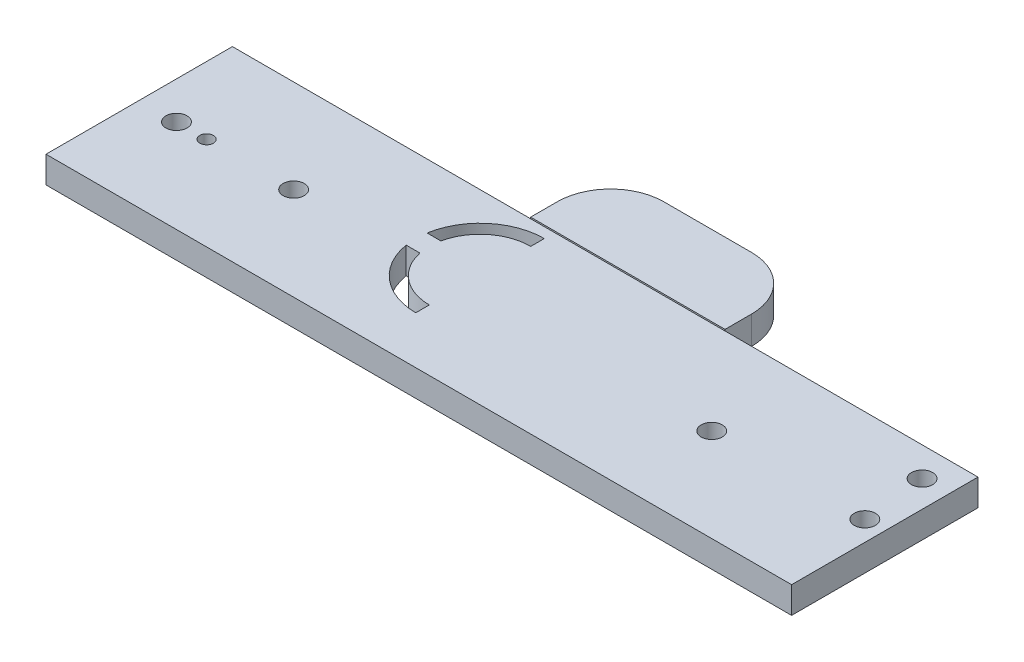
SolidWorks part; units mm, degrees
ref_plane "Front Plane" through (0, 0, 0) normal (0, 0, 1) x (1, 0, 0)
ref_plane "Top Plane" through (0, 0, 0) normal (0, 1, 0) x (1, 0, 0)
ref_plane "Right Plane" through (0, 0, 0) normal (1, 0, 0) x (0, 0, -1)
sketch "Sketch1" plane through (0, 0, 0) normal (0, 1, 0) x (1, 0, 0)
  line L1 (0, 0) -> (280, 0)
  line L2 (0, 0) -> (0, 70)
  line L3 (0, 70) -> (280, 70)
  line L4 (280, 0) -> (280, 70)
  circle A0 centre (14, 35) radius 3.9688
  circle A1 centre (58, 35) radius 3.9688
  circle A2 centre (215, 35) radius 3.9687
  circle A3 centre (272.5, 35) radius 3.9687
  circle A5 centre (270, 59) radius 3.9688
  circle A6 centre (58, 35) radius 27.5336
  circle A7 centre (215, 35) radius 27.5336
  circle A8 centre (25.3189, 35) radius 2.55
  circle A9 centre (215, 35) radius 50.34
  dimension "D3" = 7.9375
  dimension "D6" = 58
  dimension "D7" = 7.9375
  dimension "D9" = 7.9375
  dimension "D12" = 7.5
  dimension "D13" = 7.9375
  dimension "D15" = 7.9375
  dimension "D18" = 55.0672
  dimension "D19" = 55.0672
  dimension "D20" = 5.1
  dimension "D23" = 100.68
  dimension "D1" = 280
  dimension "D2" = 70
  dimension "D4" = 35
  dimension "D5" = 14
  dimension "D8" = 35
  dimension "D10" = 215
  dimension "D11" = 35
  dimension "D14" = 35
  dimension "D16" = 11
  dimension "D17" = 10
  dimension "D21" = 35
  dimension "D22" = 32.6811
extrude "Boss-Extrude7" add sketch "Sketch1" along normal blind 10 contours A9 L3 L2 L1 A8 A6 A0 | A9 L1 L4 L3 A3 A5 | A7 A2 | L1 A9 L3 A7 | A6 A1 region at (91.8381, 0, -35) region at (165.8862, 0, -35) region at (262.3681, 0, -15.8385) region at (31.2452, 0, -35) region at (188.2452, 0, -35)
sketch "Sketch2" plane through (0, 0, -70) normal (0, 0, -1) x (-1, 0, 0)
  line L0 (55, 0) -> (-55, 0) construction
  line L1 (-185, 10.5383) -> (-112, 10.5383)
  line L2 (-185, 10.5383) -> (-185, 0)
  line L3 (-185, 0) -> (-112, 0)
  line L4 (-112, 10.5383) -> (-112, 0)
  line L5 (-280, 10) -> (-280, 0) construction
  dimension "D1" = 73
  dimension "D2" = 10.5383
  dimension "D3" = 95
extrude "Boss-Extrude8" add sketch "Sketch2" along normal blind 30
fillet "Fillet3" radius 20 1 edges at (185, 5.2692, -100)
fillet "Fillet4" radius 20 1 edges at (112, 5.2692, -100)
sketch "Sketch3" plane through (0, 10, 0) normal (0, 1, 0) x (1, 0, 0)
  line L0 (0, 70) -> (112, 70) construction
  line L1 (121, 66.13) -> (121, 17.87)
  line L3 (94.6526, 45.9399) -> (104.606, 45.9399)
  line L4 (94.6526, 45.9399) -> (94.6526, 38.0601)
  line L5 (94.6526, 38.0601) -> (104.606, 38.0601)
  line L6 (104.606, 45.9399) -> (104.606, 38.0601)
  circle A0 centre (121, 42) radius 24.13
  circle A1 centre (215, 35) radius 3.9687 construction
  circle A2 centre (121, 42) radius 19.05
  point P13 (94.6526, 42)
  point P14 (104.606, 42)
  dimension "D1" = 48.26
  dimension "D4" = 38.1
  dimension "D2" = 94
  dimension "D3" = 28
  dimension "D5" = 28
  dimension "D6" = 9.9534
  dimension "D7" = 7.8798
  dimension "D8" = 16.394
extrude "Cut-Extrude1" cut sketch "Sketch3" against normal through all contours A2 L1 A0 L3 region at (108.2053, 10, -57.3734)
extrude "Cut-Extrude2" cut sketch "Sketch3<3>" against normal through all contours A2 L5 A0 L1 region at (108.2053, 10, -26.6266)
sketch "Sketch3<3>" plane through (0, 10, 0) normal (0, 1, 0) x (1, 0, 0) same geometry as "Sketch3"
